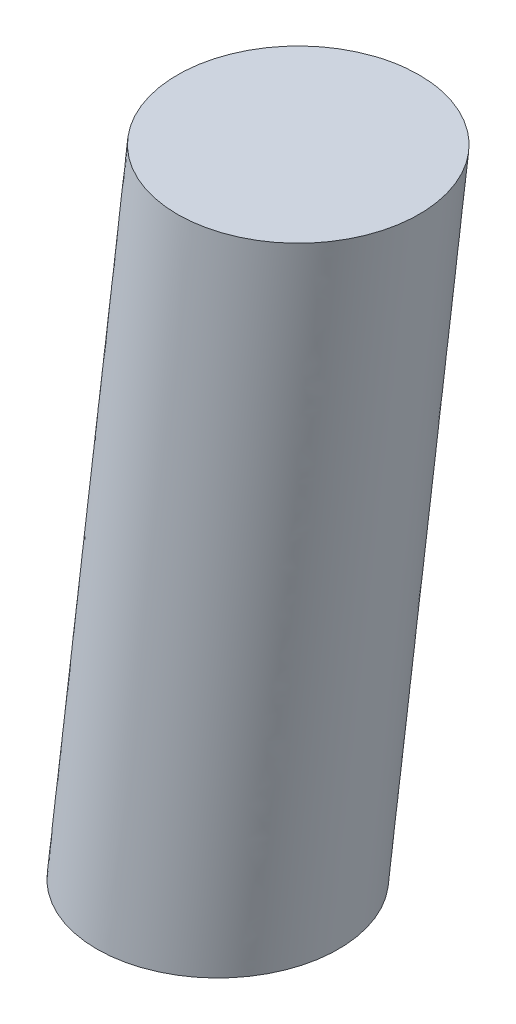
SolidWorks part; units mm, degrees
ref_plane "前基準面" through (0, 0, 0) normal (0, 0, 1) x (1, 0, 0)
ref_plane "上基準面" through (0, 0, 0) normal (0, 1, 0) x (1, 0, 0)
ref_plane "右基準面" through (0, 0, 0) normal (1, 0, 0) x (0, 0, -1)
sketch "草圖1" plane through (0, 0, 0) normal (0, 0, 1) x (1, 0, 0)
  line L0 (75, 0) -> (100, 210)
  dimension "D1" = 75
  dimension "D2" = 100
  dimension "D3" = 210
sketch "草圖2" plane through (0, 0, 0) normal (0, 1, 0) x (1, 0, 0)
  circle A0 centre (75, 0) radius 37.5
  dimension "D1" = 75
sweep "掃出1" add profiles "草圖2" path "草圖1"
ref_axis "基準軸1" through (0, -12.5, 0) along (0, 1, 0)
